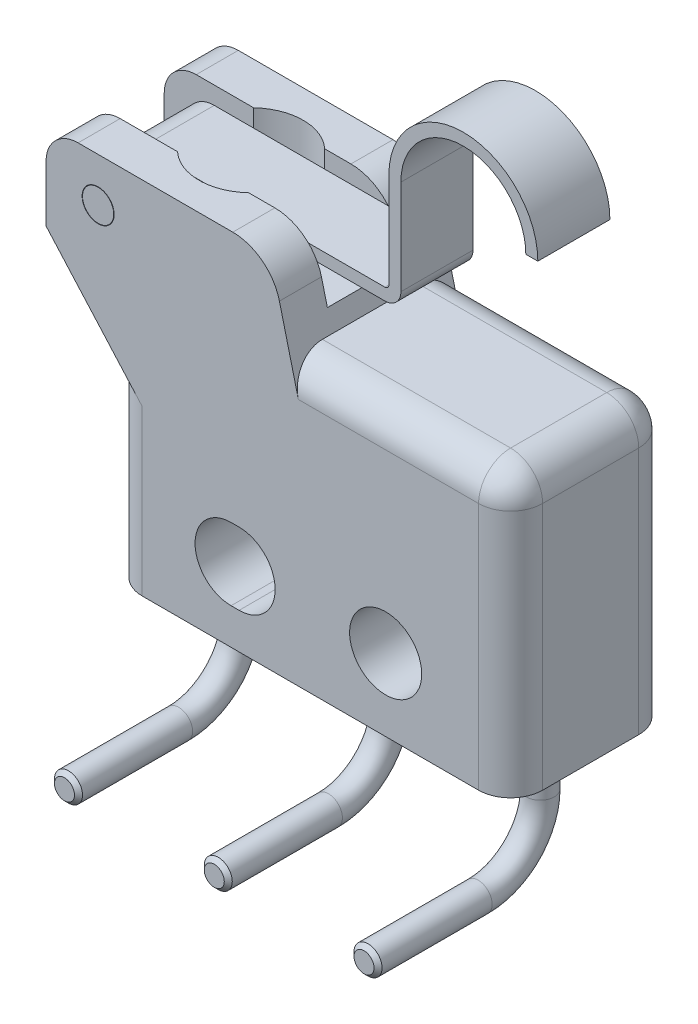
SolidWorks part; units mm, degrees
ref_plane "Front" through (0, 0, 0) normal (0, 0, 1) x (1, 0, 0)
ref_plane "Top" through (0, 0, 0) normal (0, 1, 0) x (1, 0, 0)
ref_plane "Right" through (0, 0, 0) normal (1, 0, 0) x (0, 0, -1)
sketch "Sketch4" plane through (0, 0, 0) normal (0, 0, 1) x (1, 0, 0)
  line L0 (0, 0) -> (12.7, 0)
  line L1 (12.7, 0) -> (12.7, 8.89)
  line L2 (12.7, 8.89) -> (5.715, 8.89)
  line L3 (5.715, 8.89) -> (5.08, 11.43)
  line L4 (5.08, 11.43) -> (-2.032, 11.43)
  line L5 (-2.032, 11.43) -> (-2.032, 8.636)
  line L6 (-2.032, 8.636) -> (0, 6.35)
  line L7 (0, 6.35) -> (0, 0)
  dimension "D1" = 12.7
  dimension "D2" = 8.89
  dimension "D3" = 11.43
  dimension "D4" = 14.732
  dimension "D5" = 6.35
  dimension "D6" = 8.636
  dimension "D7" = 6.985
  dimension "D8" = 7.62
extrude "Boss-Extrude3" add sketch "Sketch4" along normal blind 5.08
sketch "Sketch5" plane through (0, 0, 5.08) normal (0, 0, 1) x (1, 0, 0)
  line L0 (3.8354, 2.286) -> (4.0894, 2.286) construction
  line L1 (3.8354, 3.429) -> (4.0894, 3.429)
  line L2 (3.8354, 1.143) -> (4.0894, 1.143)
  line L3 (12.7, 0) -> (12.7, 8.89) construction
  line L4 (-2.032, 11.43) -> (-2.032, 8.636) construction
  circle A0 centre (8.7376, 2.286) radius 1.143
  arc A1 (3.8354, 3.429) -> (3.8354, 1.143) centre (3.8354, 2.286) ccw
  arc A2 (4.0894, 1.143) -> (4.0894, 3.429) centre (4.0894, 2.286) ccw
  circle A3 centre (-0.381, 10.033) radius 0.508
  point P4 (3.9624, 2.286)
  dimension "D1" = 2.286
  dimension "D2" = 4.7752
  dimension "D4" = 1.143
  dimension "D9" = 1.016
  dimension "D3" = 3.9624
  dimension "D5" = 0.254
  dimension "D6" = 2.286
  dimension "D7" = 7.747
  dimension "D8" = 1.651
extrude "Cut-Extrude1" cut sketch "Sketch5" against normal through all
sketch "Sketch6" plane through (0, 11.43, 0) normal (0, 1, 0) x (1, 0, 0)
  line L0 (-2.032, -1.3335) -> (0.8034, -1.3335)
  line L1 (-2.032, -5.08) -> (-2.032, 0) construction
  line L2 (5.842, -1.3335) -> (5.842, -3.7465)
  line L3 (5.842, -3.7465) -> (3.0574, -3.7465)
  line L4 (-2.032, -3.7465) -> (-2.032, -1.3335)
  line L5 (0.8034, -3.7465) -> (-2.032, -3.7465)
  line L6 (3.0574, -1.3335) -> (5.842, -1.3335)
  arc A0 (3.0574, -1.3335) -> (0.8034, -1.3335) centre (1.9304, -2.54) ccw
  arc A1 (0.8034, -3.7465) -> (3.0574, -3.7465) centre (1.9304, -2.54) ccw
  dimension "D6" = 3.302
  dimension "D1" = 1.3335
  dimension "D2" = 2.413
  dimension "D3" = 7.874
  dimension "D4" = 3.9624
  dimension "D5" = 1.2065
extrude "Cut-Extrude2" cut sketch "Sketch6" against normal blind 1.905
sketch "Sketch7" plane through (0, 9.525, 0) normal (0, 1, 0) x (1, 0, 0)
  line L0 (-2.032, -1.3335) -> (0, -1.3335)
  line L1 (0.8034, -1.3335) -> (-2.032, -1.3335) construction
  line L2 (0, -1.3335) -> (0, -3.7465)
  line L3 (-2.032, -3.7465) -> (0.8034, -3.7465) construction
  line L4 (0, -5.08) -> (0, 0) construction
  line L5 (0, -3.7465) -> (-2.032, -3.7465)
  line L6 (-2.032, -3.7465) -> (-2.032, -1.3335)
extrude "Cut-Extrude3" cut sketch "Sketch7" against normal through all
sketch "Sketch8" plane through (0, 0, 5.08) normal (0, 0, 1) x (1, 0, 0)
  circle A0 centre (-0.381, 10.033) radius 0.4953
  dimension "D1" = 0.9906
extrude "Boss-Extrude4" add sketch "Sketch8" against normal up to surface (5.08 mm away) up to face at (0.127, 10.033, 0)
sketch "Sketch9" plane through (0, 9.525, 0) normal (0, 1, 0) x (1, 0, 0)
  circle A0 centre (1.9304, -2.54) radius 1.5875
  dimension "D1" = 3.175
extrude "Boss-Extrude5" add sketch "Sketch9" along normal blind 0.254
sketch "Sketch10" plane through (0, 9.779, 0) normal (0, 1, 0) x (1, 0, 0)
  circle A0 centre (1.9304, -2.54) radius 0.7874
  dimension "D1" = 1.5748
extrude "Boss-Extrude6" add sketch "Sketch10" along normal blind 0.7112
ref_plane "Plane1" through (0, 0, 1.397) normal (0, 0, 1) x (1, 0, 0)
sketch "Sketch11" plane through (0, 0, 1.397) normal (0, 0, 1) x (1, 0, 0)
  line L0 (-0.381, 10.5537) -> (7.3152, 10.5537)
  line L1 (7.8232, 11.0617) -> (7.8232, 14.0716)
  line L2 (9.8044, 14.0716) -> (12.7054, 14.0716) construction
  line L3 (-0.381, 10.033) -> (-0.2079, 9.2826) construction
  line L4 (7.4422, 11.0617) -> (7.4422, 14.0716)
  line L5 (-0.381, 10.9347) -> (7.3152, 10.9347)
  line L6 (-0.264, 9.5256) -> (-0.1783, 9.1544)
  line L7 (11.7856, 14.0716) -> (12.1666, 14.0716)
  arc A0 (11.7856, 14.0716) -> (7.8232, 14.0716) centre (9.8044, 14.0716) ccw
  circle A1 centre (8.7376, 2.286) radius 1.143 construction
  arc A2 (7.8232, 11.0617) -> (7.3152, 10.5537) centre (7.3152, 11.0617) cw
  arc A3 (-0.381, 10.5537) -> (-0.264, 9.5256) centre (-0.381, 10.033) ccw
  arc A4 (12.1666, 14.0716) -> (7.4422, 14.0716) centre (9.8044, 14.0716) ccw
  arc A5 (7.4422, 11.0617) -> (7.3152, 10.9347) centre (7.3152, 11.0617) cw
  arc A6 (-0.381, 10.9347) -> (-0.1783, 9.1544) centre (-0.381, 10.033) ccw
  dimension "D1" = 1.0668
  dimension "D2" = 3.9624
  dimension "D3" = 0.508
  dimension "D4" = 1.0414
  dimension "D6" = 14.1478
  dimension "D5" = 0.381
extrude "Boss-Extrude7" add sketch "Sketch11" along normal blind 2.286 separate body
ref_plane "Plane2" through (6.35, 0, 0) normal (1, 0, 0) x (0, 0, -1)
ref_plane "Plane3" through (0, 0, 2.54) normal (0, 0, 1) x (1, 0, 0)
sketch "Sketch13" plane through (0, 0, 0) normal (0, -1, 0) x (1, 0, 0)
  line L0 (6.35, -50) -> (6.35, 50) construction
  line L1 (50, 2.54) -> (-50, 2.54) construction
  circle A0 centre (6.35, 2.54) radius 0.4445
  dimension "D1" = 0.889
ref_plane "Plane4" through (0, 0, 8.128) normal (0, 0, 1) x (1, 0, 0)
sketch "Sketch14" plane through (0, 0, 8.128) normal (0, 0, 1) x (1, 0, 0)
  line L0 (6.35, -50) -> (6.35, 50) construction
  line L1 (0, 0) -> (12.7, 0) construction
  circle A0 centre (6.35, -3.4925) radius 0.4445
  dimension "D1" = 0.889
  dimension "D2" = 3.937
sketch "Sketch15" plane through (6.35, 0, 0) normal (1, 0, 0) x (0, 0, -1)
  line L0 (-2.54, 0) -> (-2.54, -1.524)
  line L1 (-2.9845, 0) -> (-2.0955, 0) construction
  line L2 (-2.54, 50) -> (-2.54, -50) construction
  line L3 (-4.5085, -3.4925) -> (-8.128, -3.4925)
  line L4 (-8.128, 50) -> (-8.128, -50) construction
  arc A0 (-2.54, -1.524) -> (-4.5085, -3.4925) centre (-4.5085, -1.524) cw
  point P9 (-2.54, -3.4925)
  dimension "D1" = 1.9685
sweep "Sweep1" add profiles "Sketch13" path "Sketch15"
chamfer "Chamfer1" distance 0.127 angle 45 1 edges at (6.35, -3.937, 8.128)
pattern_linear "LPattern1" count 2 spacing 4.7498 along (1, 0, 0) count 2 spacing 4.7498 along (-1, 0, 0) of "Sweep1", "Chamfer1"
fillet "Fillet1" radius 1.016 9 edges at (9.2075, 8.89, 0) (9.2075, 8.89, 5.08) (12.7, 4.445, 0) (0, 3.175, 0) (0, 3.175, 5.08) (12.7, 4.445, 5.08) (-2.032, 11.43, 0.6667) (-2.032, 11.43, 4.4133) (12.7, 8.89, 2.54)
fillet "Fillet2" radius 1.524 2 edges at (5.08, 11.43, 0.6667) (5.08, 11.43, 4.4133)
sketch "Sketch16" plane through (0, 0, 0) normal (0, -1, 0) x (1, 0, 0)
  text T0 "<r90>C</r>" font "Century Gothic" height in points 5
extrude "Cut-Extrude4" cut sketch "Sketch16" against normal blind 0.0254
sketch "Sketch17" plane through (0, 0, 0) normal (0, -1, 0) x (1, 0, 0)
  text T0 "<r90>NC</r>" font "Century Gothic" height in points 5
extrude "Cut-Extrude5" cut sketch "Sketch17" against normal blind 0.0254
sketch "Sketch18" plane through (0, 0, 0) normal (0, -1, 0) x (1, 0, 0)
  text T0 "<r90>NO</r>" font "Century Gothic" height in points 5
extrude "Cut-Extrude6" cut sketch "Sketch18" against normal blind 0.0254
ref_axis "Axis1" through (1.6002, -3.4925, 4.5085) along (0, 0, 1)
ref_axis "Axis2" through (11.0998, -3.4925, 4.5085) along (0, 0, 1)
ref_point "Point1"
ref_point "Point2"
ref_axis "Axis3" through (1.6002, -1.524, 2.54) along (0, 1, 0)
ref_axis "Axis4" through (11.0998, -1.524, 2.54) along (0, 1, 0)
